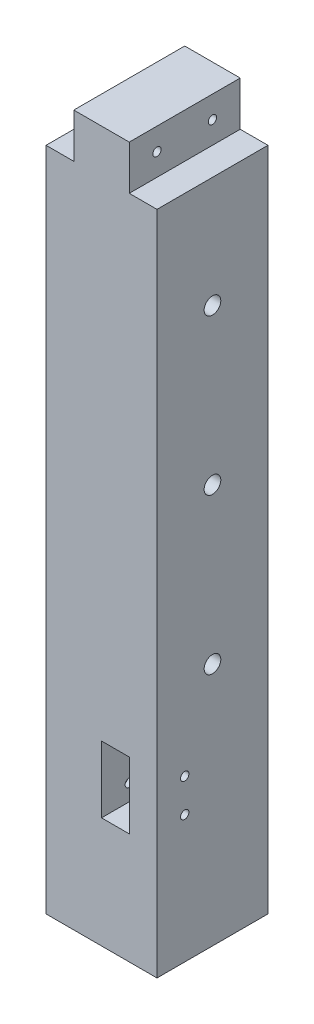
SolidWorks part; units mm, degrees
material "Pine"
ref_plane "Front Plane" through (0, 0, 0) normal (0, 0, 1) x (1, 0, 0)
ref_plane "Top Plane" through (0, 0, 0) normal (0, 1, 0) x (1, 0, 0)
ref_plane "Right Plane" through (0, 0, 0) normal (1, 0, 0) x (0, 0, -1)
sketch "Sketch1" plane through (0, 0, 0) normal (0, 0, 1) x (1, 0, 0)
  line L1 (63.5, 381) -> (-63.5, 381)
  line L2 (63.5, 381) -> (63.5, -381)
  line L3 (63.5, -381) -> (-63.5, -381)
  line L4 (-63.5, 381) -> (-63.5, -381)
  line L5 (63.5, 381) -> (-63.5, -381) construction
  line L6 (63.5, -381) -> (-63.5, 381) construction
  line L7 (31.75, 431.8) -> (-31.75, 431.8)
  line L8 (31.75, 431.8) -> (31.75, 330.2)
  line L9 (31.75, 330.2) -> (-31.75, 330.2)
  line L10 (-31.75, 431.8) -> (-31.75, 330.2)
  line L11 (31.75, 431.8) -> (-31.75, 330.2) construction
  line L12 (31.75, 330.2) -> (-31.75, 431.8) construction
  point P0 (0, 0)
  point P6 (0, 381)
  dimension "D1" = 101.6
  dimension "D2" = 812.8
  dimension "D3" = 127
  dimension "D4" = 63.5
extrude "Boss-Extrude1" add sketch "Sketch1" along normal blind 127 contours L10 L1 L4 L3 L2 L8 L9 | L1 L10 L9 L8 | L7 L10 L1 L8 region at (0, -12.2621, 0) region at (0, 355.6, 0) region at (0, 406.4, 0)
sketch "Sketch2" plane through (0, 0, 127) normal (0, 0, 1) x (1, 0, 0)
  line L0 (63.5, 381) -> (63.5, -381) construction
  line L1 (31.75, -177.8) -> (0, -177.8)
  line L2 (31.75, -177.8) -> (31.75, -254)
  line L3 (31.75, -254) -> (0, -254)
  line L4 (0, -177.8) -> (0, -254)
  line L5 (31.75, -177.8) -> (0, -254) construction
  line L6 (31.75, -254) -> (0, -177.8) construction
  line L7 (63.5, -381) -> (-63.5, -381) construction
  point P0 (15.875, -215.9)
  dimension "D1" = 31.75
  dimension "D2" = 76.2
  dimension "D3" = 31.75
  dimension "D4" = 127
extrude "Cut-Extrude1" cut sketch "Sketch2" against normal blind 63.5
sketch "Sketch3" plane through (-63.5, 0, 0) normal (-1, 0, 0) x (0, 0, 1)
  line L0 (0, 381) -> (0, -381) construction
  line L1 (63.5, -177.8) -> (31.75, -177.8)
  line L2 (63.5, -177.8) -> (63.5, -254)
  line L3 (63.5, -254) -> (31.75, -254)
  line L4 (31.75, -177.8) -> (31.75, -254)
  line L5 (63.5, -177.8) -> (31.75, -254) construction
  line L6 (63.5, -254) -> (31.75, -177.8) construction
  line L7 (127, -381) -> (0, -381) construction
  point P0 (47.625, -215.9)
  dimension "D1" = 76.2
  dimension "D2" = 31.75
  dimension "D3" = 127
  dimension "D4" = 31.75
extrude "Cut-Extrude3" cut sketch "Sketch3" against normal blind 63.246
sketch "Sketch4" plane through (-63.5, 0, 0) normal (-1, 0, 0) x (0, 0, 1)
  line L0 (63.5, 381) -> (63.5, -49619) construction
  line L1 (127, 381) -> (0, 381) construction
  line L2 (127, -381) -> (0, -381) construction
  circle A0 centre (63.5, -101.6) radius 9.525
  circle A1 centre (63.5, 76.2) radius 9.525
  circle A2 centre (63.5, 254) radius 9.525
  point P4 (63.5, 381)
  dimension "D1" = 19.05
  dimension "D2" = 177.8
  dimension "D3" = 177.8
  dimension "D4" = 279.4
extrude "Cut-Extrude4" cut sketch "Sketch4" against normal through all
sketch "Sketch5" plane through (0, 0, 0) normal (0, 0, -1) x (-1, 0, 0)
  line L0 (31.75, -177.8) -> (31.75, -254) construction
  line L4 (63.5, -254) -> (63.5, -177.8)
  line L5 (0.254, -254) -> (63.5, -254)
  line L6 (0.254, -177.8) -> (0.254, -254)
  line L7 (63.5, -177.8) -> (0.254, -177.8)
  line L8 (63.5, -254) -> (63.5, -177.8)
  line L9 (0.254, -254) -> (63.5, -254)
  line L10 (0.254, -177.8) -> (0.254, -254)
  line L11 (63.5, -177.8) -> (0.254, -177.8)
  circle A0 centre (31.75, -234.95) radius 4.7625
  circle A1 centre (31.75, -196.85) radius 4.7625
  point P10 (31.75, -215.9)
  dimension "D4" = 9.525
  dimension "D2" = 19.05
  dimension "D3" = 19.05
  dimension "D5" = 31.75
  dimension "D1" = 0
extrude "Cut-Extrude5" cut sketch "Sketch5" against normal blind 69.85 contours A0 L0 | L0 A0 | A1 L0 | L0 A1 region at (-33.7713, -196.85, 0) region at (-29.7287, -196.85, 0) region at (-33.7713, -234.95, 0) region at (-29.7287, -234.95, 0)
sketch "Sketch6" plane through (63.5, 0, 0) normal (1, 0, 0) x (0, 0, -1)
  line L0 (-95.25, -177.8) -> (-95.25, -254) construction
  line L4 (-127, -177.8) -> (-127, -254)
  line L5 (-63.5, -177.8) -> (-127, -177.8)
  line L6 (-63.5, -254) -> (-63.5, -177.8)
  line L7 (-127, -254) -> (-63.5, -254)
  line L8 (-127, -177.8) -> (-127, -254)
  line L9 (-63.5, -177.8) -> (-127, -177.8)
  line L10 (-63.5, -254) -> (-63.5, -177.8)
  line L11 (-127, -254) -> (-63.5, -254)
  circle A0 centre (-95.25, -234.95) radius 4.7625
  circle A1 centre (-95.25, -196.85) radius 4.7625
  point P10 (-95.25, -215.9)
  dimension "D3" = 19.05
  dimension "D4" = 9.525
  dimension "D2" = 19.05
  dimension "D5" = 31.75
  dimension "D1" = 0
extrude "Cut-Extrude6" cut sketch "Sketch6" against normal blind 69.85 contours A1 L0 | L0 A1 | A0 L0 | L0 A0 region at (63.5, -196.85, 93.2287) region at (63.5, -196.85, 97.2713) region at (63.5, -234.95, 93.2287) region at (63.5, -234.95, 97.2713)
sketch "Sketch7" plane through (31.75, 0, 0) normal (1, 0, 0) x (0, 0, -1)
  line L0 (-127, 406.4) -> (0, 406.4) construction
  line L1 (-127, 431.8) -> (-127, 381) construction
  line L2 (0, 431.8) -> (0, 381) construction
  circle A0 centre (-95.25, 406.4) radius 4.7625
  circle A1 centre (-31.75, 406.4) radius 4.7625
  point P10 (-63.5, 406.4)
  dimension "D1" = 31.75
  dimension "D3" = 9.525
  dimension "D2" = 31.75
extrude "Cut-Extrude7" cut sketch "Sketch7" against normal through all
